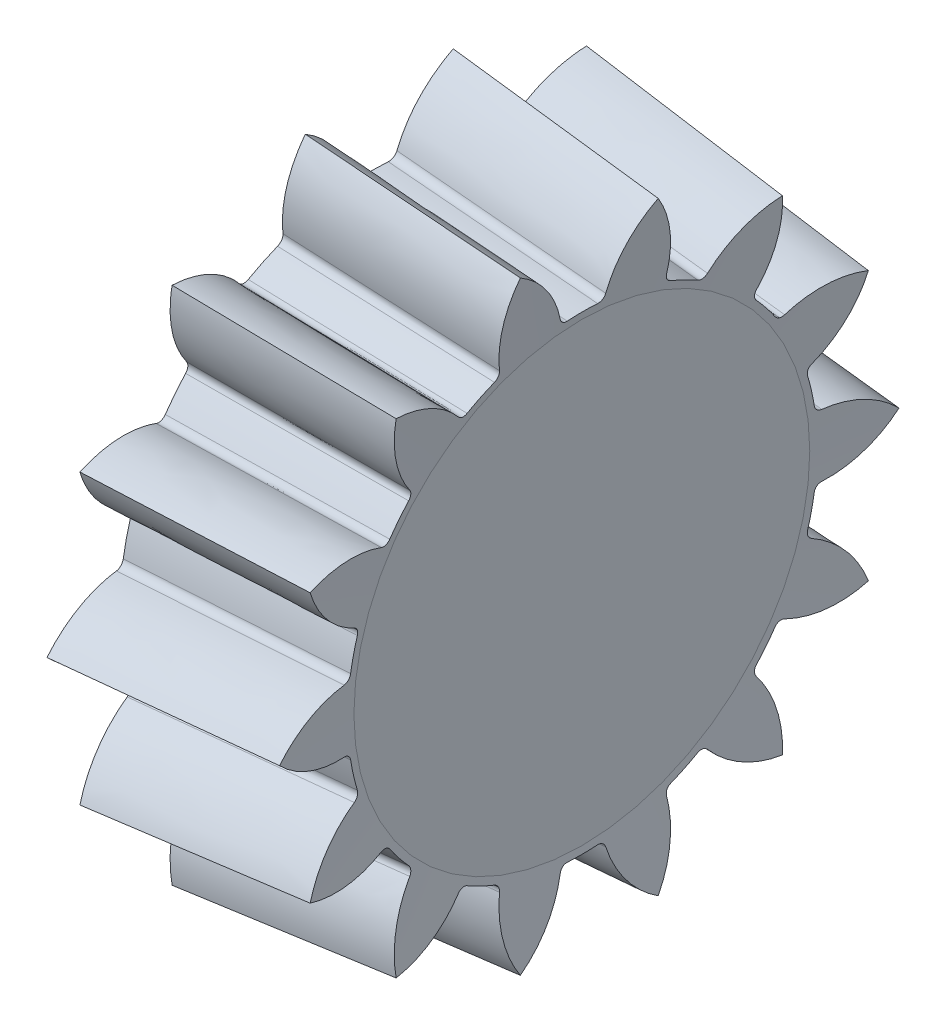
SolidWorks part; units mm, degrees
revolve "Base-Revolve" add sketch "BasProSke" angle 360 about L0 other way angle 12.857
sketch "BasProSke" plane through (0, 0, 0) normal (0, 1, 0) x (1, 0, 0)
  line L0 (-10, 0) -> (60, 0) construction
  line L1 (0, 0) -> (0, 44.1255)
  line L2 (0, 0) -> (37.9847, 0)
  line L3 (37.9847, 0) -> (37.9847, 41.1293)
  line L4 (559.4068, 0) -> (-30.9725, 53.6708) construction
  line L5 (0, 44.1255) -> (1.5635, 61.3244)
  line L6 (559.4068, 0) -> (189.4823, 40.6663) construction
  line L7 (559.4068, 0) -> (0, 44.1255) construction
  line L8 (1.5635, 61.3244) -> (39.4421, 57.1604)
  line L9 (39.4421, 57.1604) -> (37.9847, 41.1293)
  line L10 (0.6068, 50.8) -> (-11.3776, 50.8) construction
  dimension "Addendum" = 10.5678
  dimension "Pitch_rad" = 50.8
  dimension "Dedendum_plus" = 6.702
  dimension "Face_wid" = 38.1
  dimension "Pitch_ang" = 5.194
  dimension "D1" = 88.2511
  dimension "D2" = 559.4068
  dimension "D3" = 561.1043
  dimension "D4" = 1.079
ref_plane "Plane1" through (0, 0, 0) normal (0, 0, 1) x (1, 0, 0)
ref_plane "Plane2" through (0, 0, 0) normal (0, 1, 0) x (1, 0, 0)
ref_plane "Plane3" through (0, 0, 0) normal (1, 0, 0) x (0, 0, -1)
sketch "HoldingSke" plane through (0, 0, 0) normal (0, 1, 0) x (1, 0, 0)
  line L0 (0, 0) -> (86.2593, -21.5069)
  line L1 (-15, 0) -> (100, 0) construction
  line L2 (0, 0) -> (629.4298, -165.5916)
  line L3 (0, 0) -> (-11.863, 4.5341)
  line L4 (0, 0) -> (8.3795, 2.0892)
  line L5 (0, 0) -> (-47.5972, -17.7524)
  line L6 (0, 0) -> (-10.5278, -7.1032)
  line L7 (629.4298, -165.5916) -> (970.5161, -608.9836)
  line L8 (-76.2, 54.61) -> (-61.976, 54.61)
  line L9 (-71.009, 38.7566) -> (-53.1078, 45.2721)
  line L10 (-76.2, 71.12) -> (104.1128, 71.12)
  line L11 (0, 0) -> (-38.1, 0)
  line L12 (-76.2, 101.6) -> (-75.9079, 101.6)
  line L13 (24.9733, 27.94) -> (52.9471, 28.6511)
  line L14 (24.9733, 27.94) -> (25.0241, 27.9398)
  line L15 (24.9733, 27.94) -> (100.4124, 28.9036)
  line L16 (629.4298, -165.5916) -> (513.3889, -222.1885)
  circle A0 centre (0, 0) radius 6.35
  circle A1 centre (0, 0) radius 38.1
  circle A2 centre (0, 0) radius 38.1
  circle A3 centre (0, 0) radius 6.35
  dimension "MHD" = 76.2
  dimension "Hub_dia" = 76.2
  dimension "Bore" = 12.7
  dimension "MBD" = 12.7
  dimension "Num_teeth" = 14
  dimension "Pitch" = 88.9
  dimension "Mounting_dist" = 50.8
  dimension "Show_teeth" = 14
  dimension "Thickness" = 12.7
  dimension "OAL" = 559.4071
  dimension "T_dim" = 14.224
  dimension "Ap" = 20
  dimension "H" = 19.05
  dimension "Pitch_radius" = 180.3128
  dimension "Width" = 38.1
  dimension "Backlash" = 0.2921
  dimension "Addendum_fac" = 1.456
  dimension "Dedendum_fac" = 0.732
  dimension "Clearance_fac" = 0.188
  dimension "Dedendum_add" = 0.0508
  dimension "Mating_teeth" = 154
  dimension "MnMD" = 559.4068
ref_plane "ToothPln" through (0.7818, 52.725, 0) normal (-0.9959, 0.0905, 0) x (0, 0, -1)
ref_plane "ToothPln2" through (554.8215, -50.4383, 0) normal (-0.9959, 0.0905, 0) x (0, 0, 1)
sketch "TooCutSke" plane through (0.7818, 52.725, 0) normal (-0.9959, 0.0905, 0) x (0, 0, -1)
  line L2 (0, 52.7329) -> (386.8442, -1642.142) construction
  line L3 (0, 52.7329) -> (209.164, -1756.5915) construction
  line L4 (0, -15.621) -> (0, 105.791) construction
  line L6 (-24.765, -8.6349) -> (21.082, -8.6349) construction
  line L7 (11.3041, 3.2066) -> (5.799, 2.5702) construction
  arc A0 (-16.9257, -7.5305) -> (16.9257, -7.5305) centre (0, 52.7329) ccw
  arc A1 (-2.9386, 7.3896) -> (2.9386, 7.3896) centre (0, 52.7329) ccw
  circle A2 centre (0, 52.7329) radius 50.8 construction
  circle A3 centre (0, 52.7329) radius 47.7364 construction
  arc A4 (4.3988, 6.3369) -> (2.9386, 7.3896) centre (3.0301, 5.9775) ccw
  arc A5 (4.3988, 6.3369) -> (16.9257, -7.5305) centre (24.0523, 11.4988) ccw
  arc A6 (-16.9257, -7.5305) -> (-4.3988, 6.3369) centre (-24.0523, 11.4988) ccw
  arc A7 (-2.9386, 7.3896) -> (-4.3988, 6.3369) centre (-3.0301, 5.9775) ccw
  ellipse E0 centre (0, 52.4377) end of major axis (61.3244, 52.4377) minor radius 61.0726 construction
sketch "TooCutSke2" plane through (554.8215, -50.4383, 0) normal (-0.9959, 0.0905, 0) x (0, 0, 1)
  line L0 (0, 0) -> (0, 68.072) construction
  line L2 (21.082, 43.9443) -> (-20.32, 43.9443) construction
  circle A0 centre (0, 50.6463) radius 0.0127
  ellipse E1 centre (0, 0) end of major axis (-44.1255, 0) minor radius 43.9443 construction
  dimension "Dedendum_plus" = 6.702
loft "ToothCut" cut profiles "TooCutSke2", "TooCutSke"
pattern_circular "TeethCuts" count 14 every 25.714 about axis through (-10, 0, 0) along (1, 0, 0) of "ToothCut"
scale "Scale1" scale about origin uniform scaling yes scale factor 0.35878
equation "' \"Pitch@HoldingSke\" = 4"
equation "' \"Num_teeth@HoldingSke\" = 12"
equation "' \"Mating_teeth@HoldingSke\" = 20"
equation "' \"Ap@HoldingSke\" =  20"
equation "' \"Ap@HoldingSke\" = 20"
equation "' \"Width@HoldingSke\" = 0.5"
equation "' \"Hub_dia@HoldingSke\"= 2"
equation "' \"Hub_dia@HoldingSke\" = 2"
equation "' \"Mounting_dist@HoldingSke\" = 3"
equation "' \"Bore@HoldingSke\" = 0.75"
equation "' \"T_dim@HoldingSke\" = 0.85"
equation "' \"Width@KeySke\" = 0.25"
equation "' \"Show_teeth@HoldingSke\" = 100"
equation "' \"Backlash@HoldingSke\" = 0.009"
equation "' \"Addendum_fac@HoldingSke\" = 1.0"
equation "' \"Dedendum_fac@HoldingSke\" = 1.188"
equation "' \"Dedendum_add@HoldingSke\" = 0.002"
equation "' \"Clearance_fac@HoldingSke\" = 0.188"
equation "' \"Addendum_fac@HoldingSke\" = 0.54 + 0.46 / (\"Num_teeth@HoldingSke\" /  \"Mating_teeth@HoldingSke\" ) ^ 2"
equation " \"Addendum_fac@HoldingSke\" = 2 - (0.54 + 0.46 / (\"Mating_teeth@HoldingSke\" /  \"Num_teeth@HoldingSke\" ) ^ 2)"
equation "\"Dedendum_fac@HoldingSke\" = 2.188 - \"Addendum_fac@HoldingSke\""
equation "\"Pitch_rad@BasProSke\" = \"Num_teeth@HoldingSke\" / \"Pitch@HoldingSke\" / 2"
equation "\"Pitch_ang@BasProSke\" = atn(\"Num_teeth@HoldingSke\" / \"Mating_teeth@HoldingSke\") * (180 / 3.14159265)"
equation "\"Addendum@BasProSke\" = \"Addendum_fac@HoldingSke\" / \"Pitch@HoldingSke\""
equation "\"Dedendum_plus@BasProSke\" = (\"Dedendum_fac@HoldingSke\" / \"Pitch@HoldingSke\" + \"Dedendum_add@HoldingSke\") * 1.25"
equation "\"Face_wid@BasProSke\" = \"Width@HoldingSke\""
equation "\"Radius@TooCutSke\" = ((\"Num_teeth@HoldingSke\" + 2 * \"Addendum_fac@HoldingSke\") / \"Pitch@HoldingSke\" ) / 2"
equation "\"Overcut_dia@TooCutSke\" =  1.02 * (\"Num_teeth@HoldingSke\" + 2 * \"Addendum_fac@HoldingSke\") / \"Pitch@HoldingSke\""
equation "\"Pitch_dia@TooCutSke\" = \"Num_teeth@HoldingSke\" / \"Pitch@HoldingSke\""
equation "\"Base_dia@TooCutSke\" = \"Num_teeth@HoldingSke\" / \"Pitch@HoldingSke\" * cos((\"Ap@HoldingSke\"  * 3.14159265 / 180))"
equation "'  \"Root_dia@TooCutSke\" =  (\"Num_teeth@HoldingSke\" + 2) / \"Pitch@HoldingSke\" - 2 * (\"Addendum_fac@HoldingSke\" + \"Dedendum_fac@HoldingSke\") / \"Pitch@HoldingSke\" - \"Dedendum_add@HoldingSke\" * 2"
equation "'  \"Root_dia@TooCutSke\" = (\"Num_teeth@HoldingSke\" + 2) / \"Pitch@HoldingSke\" - 2 * (\"Addendum_fac@HoldingSke\" + \"Dedendum_fac@HoldingSke\") / \"Pitch@HoldingSke\" - \"Dedendum_add@HoldingSke\" * 2"
equation "\"Root_dia@TooCutSke\" =  \"Num_teeth@HoldingSke\" / \"Pitch@HoldingSke\" -  2 * \"Dedendum_fac@HoldingSke\" / \"Pitch@HoldingSke\" - \"Dedendum_add@HoldingSke\" * 2"
equation "\"Half_ang@TooCutSke\" = 180 / \"Num_teeth@HoldingSke\""
equation "\"Half_CT@TooCutSke\" = \"Num_teeth@HoldingSke\" / \"Pitch@HoldingSke\" * sin((3.14159265 / 2 / \"Num_teeth@HoldingSke\")) / 2 - 2 * \"Backlash@HoldingSke\" / 4"
equation "\"Flank_rad@TooCutSke\" = \"Num_teeth@HoldingSke\" / \"Pitch@HoldingSke\" / 5"
equation "\"Root_fillet@TooCutSke\" = \"Clearance_fac@HoldingSke\" / \"Pitch@HoldingSke\" + \"Dedendum_add@HoldingSke\""
equation "\"Offset@ToothPln2\"  = \"Num_teeth@HoldingSke\" / \"Pitch@HoldingSke\" / 2 / sin(atn(\"Num_teeth@HoldingSke\" / \"Mating_teeth@HoldingSke\"))"
equation "\"Dedendum_plus@TooCutSke2\" = \"Dedendum_plus@BasProSke\""
equation "\"MHD@HoldingSke\" = \"Num_teeth@HoldingSke\" / \"Pitch@HoldingSke\" - 2 * \"Dedendum_plus@BasProSke\" * cos(atn(\"Num_teeth@HoldingSke\" / \"Mating_teeth@HoldingSke\"))"
equation "\"MBD@HoldingSke\" = \"Num_teeth@HoldingSke\" / \"Pitch@HoldingSke\" - 2 * \"Dedendum_plus@BasProSke\" * cos(atn(\"Num_teeth@HoldingSke\" / \"Mating_teeth@HoldingSke\")) - 0.002"
equation "\"MnMD@HoldingSke\" =  \"Num_teeth@HoldingSke\" / \"Pitch@HoldingSke\" / 2 / (\"Num_teeth@HoldingSke\" / \"Mating_teeth@HoldingSke\") + \"Dedendum_plus@BasProSke\" * sin(atn(\"Num_teeth@HoldingSke\" / \"Mating_teeth@HoldingSke\"))"
equation "\"OAL@HoldingSke\" = \"MnMD@HoldingSke\""
equation "\"MHD@HoldingSke\" = ((sgn( \"MHD@HoldingSke\" - \"Hub_dia@HoldingSke\" )-1)*( \"MHD@HoldingSke\" - \"Hub_dia@HoldingSke\" ))/-2+ \"Hub_dia@HoldingSke\""
equation "\"MBD@HoldingSke\" = ((sgn( \"MBD@HoldingSke\" - \"Bore@HoldingSke\" )-1)*( \"MBD@HoldingSke\" - \"Bore@HoldingSke\" ))/-2+ \"Bore@HoldingSke\""
equation "\"Face_wid@BasProSke\" = ((sgn( \"Face_wid@BasProSke\" - \"Offset@ToothPln2\" * 0.9)-1)*( \"Face_wid@BasProSke\" - \"Offset@ToothPln2\" * 0.9))/-2+ \"Offset@ToothPln2\" * 0.9"
equation "\"OAL@HoldingSke\" = ((sgn( \"OAL@HoldingSke\" - \"Mounting_dist@HoldingSke\" )+1)*( \"OAL@HoldingSke\" - \"Mounting_dist@HoldingSke\" ))/2 + \"Mounting_dist@HoldingSke\" + 0.000002"
equation "\"Num_teeth@TeethCuts\" = int( \"Show_teeth@HoldingSke\" ) + 1"
equation "\"Num_teeth@TeethCuts\" = ((sgn( \"Num_teeth@TeethCuts\" - \"Num_teeth@HoldingSke\" )-1)*( \"Num_teeth@TeethCuts\" - \"Num_teeth@HoldingSke\" ))/-2+ \"Num_teeth@HoldingSke\""
equation "\"Num_teeth@TeethCuts\" = ((sgn( \"Num_teeth@TeethCuts\" - 2.0)+1)*( \"Num_teeth@TeethCuts\" - 2.0))/2 +2.0"
equation "\"Angle@TeethCuts\" = 360.0 / \"Num_teeth@HoldingSke\""
